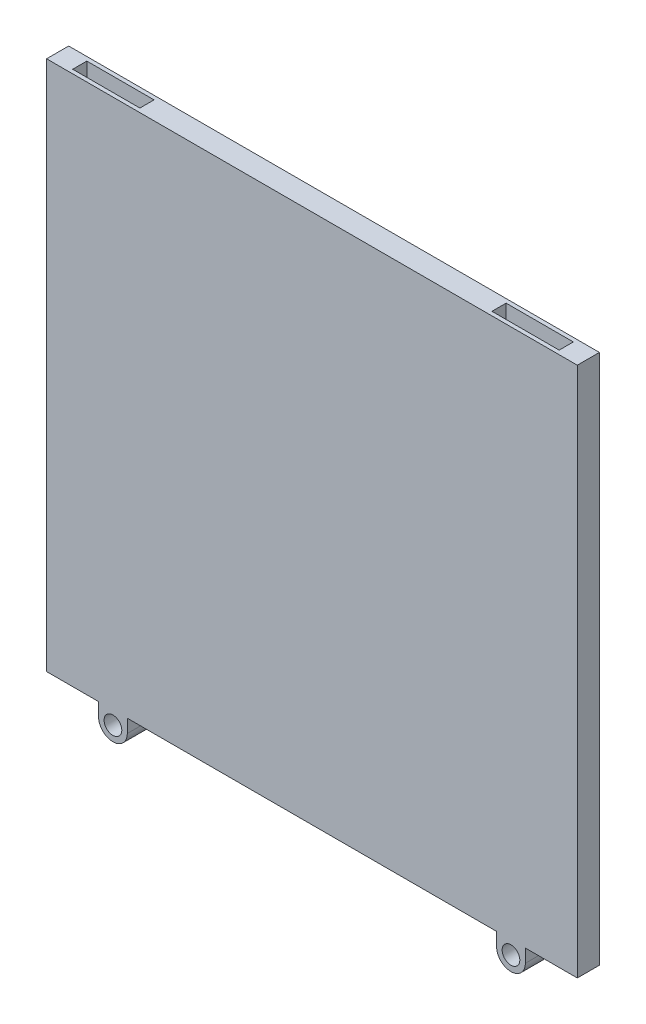
SolidWorks part; units mm, degrees
ref_plane "Front Plane" through (0, 0, 0) normal (0, 0, 1) x (1, 0, 0)
ref_plane "Top Plane" through (0, 0, 0) normal (0, 1, 0) x (1, 0, 0)
ref_plane "Right Plane" through (0, 0, 0) normal (1, 0, 0) x (0, 0, -1)
sketch "Sketch1" plane through (0, 0, 0) normal (0, 0, 1) x (1, 0, 0)
  line L1 (60, -60) -> (-60, -60)
  line L2 (60, -60) -> (60, 60)
  line L3 (60, 60) -> (-60, 60)
  line L4 (-60, -60) -> (-60, 60)
  line L5 (60, -60) -> (-60, 60) construction
  line L6 (60, 60) -> (-60, -60) construction
  point P0 (0, 0)
  dimension "D1" = 120
  dimension "D2" = 120
extrude "Boss-Extrude1" add sketch "Sketch1" along normal mid plane 5 contours L2 L3 L4 L1
sketch "Sketch4" plane through (0, 60, 0) normal (0, 1, 0) x (1, 0, 0)
  line L0 (-60, 0) -> (60, 0) construction
  line L1 (-55, -1.6) -> (-39.8, -1.6)
  line L2 (-55, -1.6) -> (-55, 1.6)
  line L3 (-55, 1.6) -> (-39.8, 1.6)
  line L4 (-39.8, -1.6) -> (-39.8, 1.6)
  line L5 (-55, -1.6) -> (-39.8, 1.6) construction
  line L6 (-55, 1.6) -> (-39.8, -1.6) construction
  line L7 (-60, -2.5) -> (-60, 2.5) construction
  line L8 (60, -2.5) -> (60, 2.5) construction
  line L9 (0, -2.75) -> (0, 2.75) construction
  line L10 (55, -1.6) -> (39.8, -1.6)
  line L11 (39.8, -1.6) -> (39.8, 1.6)
  line L12 (55, 1.6) -> (39.8, 1.6)
  line L13 (55, -1.6) -> (55, 1.6)
  point P0 (-47.4, 0)
  dimension "D1" = 15.2
  dimension "D2" = 3.2
  dimension "D3" = 5
extrude "Cut-Extrude1" cut sketch "Sketch4" against normal blind 20
sketch "Sketch6" plane through (0, 0, 2.5) normal (0, 0, 1) x (1, 0, 0)
  line L0 (60, -60) -> (-60, -60) construction
  line L1 (41.75, -60) -> (48.25, -60)
  line L2 (41.75, -60) -> (41.75, -63)
  line L4 (48.25, -60) -> (48.25, -63)
  line L5 (60, -60) -> (60, 60) construction
  arc A0 (41.75, -63) -> (48.25, -63) centre (45, -63) ccw
  circle A1 centre (45, -63) radius 2
  dimension "D2" = 4
  dimension "D4" = 3
  dimension "D1" = 6.5
  dimension "D3" = 15
extrude "Boss-Extrude2" add sketch "Sketch6" against normal up to surface (5 mm away) up to face at (0, 0, -2.5)
mirror "Mirror1" about plane through (0, 0, 0) normal (1, 0, 0) of "Boss-Extrude2"
